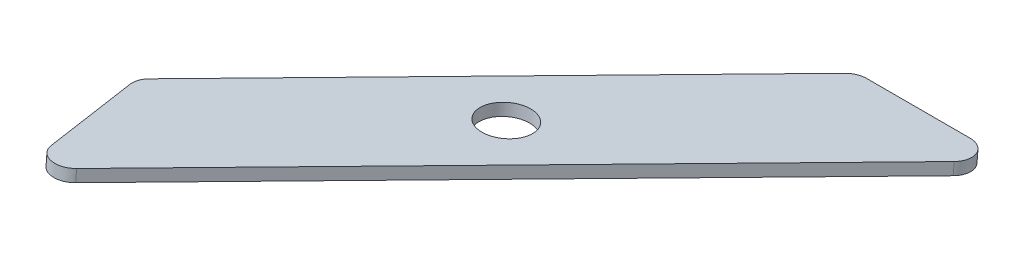
SolidWorks part; units mm, degrees
material "Plain Carbon Steel"
ref_plane "Front Plane" through (0, 0, 0) normal (0, 0, 1) x (1, 0, 0)
ref_plane "Top Plane" through (0, 0, 0) normal (0, 1, 0) x (1, 0, 0)
ref_plane "Right Plane" through (0, 0, 0) normal (1, 0, 0) x (0, 0, -1)
ref_axis "Axis1" through (323.2409, 73.7808, 63.5779) along (-0.2127, 0.0811, 0.9737)
ref_axis "Axis2" through (-330.1109, 71.1626, 32.129) along (0.2127, 0.0811, 0.9737)
ref_axis "Axis3" through (330.2, 71.12, 29.2862) along (-1, 0, 0)
ref_plane "Plane1" through (0, 68.0164, -5.6624) normal (0, -0.9966, 0.083) x (-1, 0, 0)
ref_plane "Plane2" through (0, 55.3602, -4.6088) normal (0, -0.9966, 0.083) x (-1, 0, 0)
sketch "Sketch2" plane through (0, 55.3602, -4.6088) normal (0, -0.9966, 0.083) x (-1, 0, 0)
  line L0 (255.5477, -35.0856) -> (314.7364, -108.5458)
  line L1 (-330.2, -35.0856) -> (330.2, -35.0856) construction
  line L2 (330.1109, -37.9221) -> (200.3407, -634.0279) construction
  line L3 (314.7364, -108.5458) -> (319.0729, -88.6255)
  line L4 (319.0729, -88.6255) -> (275.9345, -35.0856)
  line L5 (275.9345, -35.0856) -> (255.5477, -35.0856)
  line L6 (265.7411, -35.0856) -> (316.9047, -98.5856) construction
  line L7 (314.7364, -108.5458) -> (275.9345, -35.0856) construction
  line L8 (255.5477, -35.0856) -> (319.0729, -88.6255) construction
  circle A0 centre (291.3229, -66.8356) radius 3.2639
  dimension "D2" = 6.5278
  dimension "D3" = 31.75
  dimension "D1" = 15.875
extrude "Boss-Extrude1" add sketch "Sketch2" along normal blind 1.5875
fillet "Fillet1" radius 2.54 4 edges at (-275.9345, 57.4801, 30.4217) (-255.5477, 57.4801, 30.4217) (-319.0729, 61.9219, 83.777) (-314.7364, 63.5746, 103.6286)
